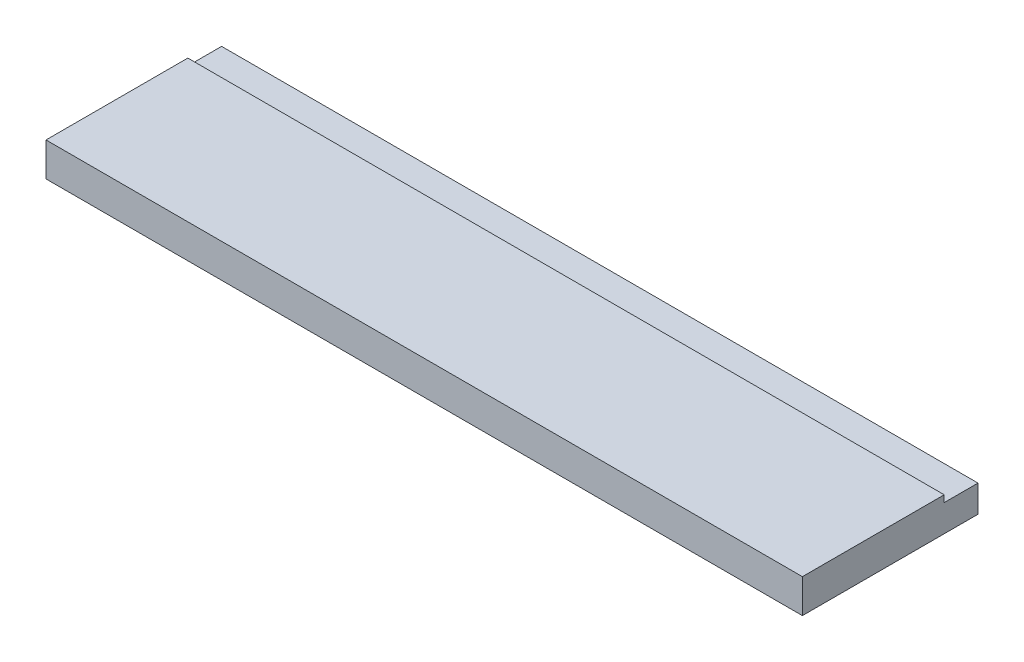
SolidWorks part; units mm, degrees
ref_plane "前视基准面" through (0, 0, 0) normal (0, 0, 1) x (1, 0, 0)
ref_plane "上视基准面" through (0, 0, 0) normal (0, 1, 0) x (1, 0, 0)
ref_plane "右视基准面" through (0, 0, 0) normal (1, 0, 0) x (0, 0, -1)
sketch "草图1" plane through (0, 0, 0) normal (0, 1, 0) x (1, 0, 0)
  line L1 (0, 52) -> (224, 52)
  line L2 (0, 52) -> (0, 0)
  line L3 (0, 0) -> (224, 0)
  line L4 (224, 52) -> (224, 0)
  dimension "D1" = 224
  dimension "D2" = 52
extrude "凸台-拉伸1" add sketch "草图1" along normal blind 10
sketch "草图2" plane through (0, 10, 0) normal (0, 1, 0) x (1, 0, 0)
  line L0 (224, 0) -> (224, 52) construction
  line L1 (0, 52) -> (224, 52)
  line L2 (0, 52) -> (0, 42)
  line L3 (0, 42) -> (224, 42)
  line L4 (224, 52) -> (224, 42)
  dimension "D1" = 10
extrude "切除-拉伸1" cut sketch "草图2" against normal blind 2
